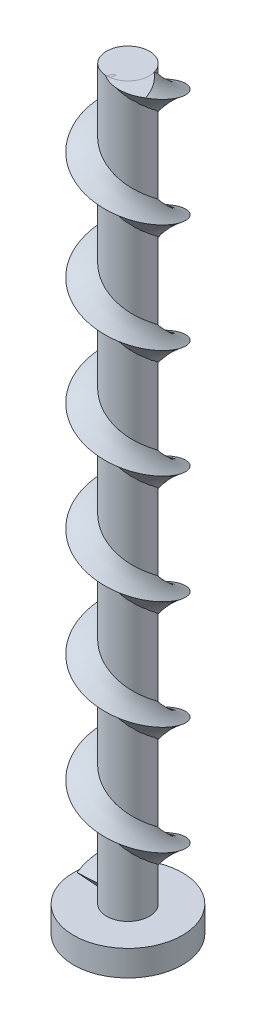
SolidWorks part; units mm, degrees
ref_plane "Front Plane" through (0, 0, 0) normal (0, 0, 1) x (1, 0, 0)
ref_plane "Top Plane" through (0, 0, 0) normal (0, 1, 0) x (1, 0, 0)
ref_plane "Right Plane" through (0, 0, 0) normal (1, 0, 0) x (0, 0, -1)
sketch "Sketch1" plane through (0, 0, 0) normal (0, 1, 0) x (1, 0, 0)
  line L1 (-2.5, 1.5) -> (2.5, 1.5)
  line L2 (-2.5, 1.5) -> (-2.5, -1.5)
  line L3 (-2.5, -1.5) -> (2.5, -1.5)
  line L4 (2.5, 1.5) -> (2.5, -1.5)
  circle A0 centre (0, 0) radius 12.7
  dimension "D1" = 5
  dimension "D2" = 3
  dimension "D3" = 1.5
  dimension "D4" = 2.5
extrude "Boss-Extrude1" add sketch "Sketch1" along normal blind 6
sketch "Sketch2" plane through (0, 6, 0) normal (0, 1, 0) x (1, 0, 0)
  circle A0 centre (0, 0) radius 5
extrude "Boss-Extrude2" add sketch "Sketch2" along normal blind 170
sketch "Sketch3" plane through (0, 6, 0) normal (0, 1, 0) x (1, 0, 0)
  circle A0 centre (0, 0) radius 5
curve "Helix/Spiral1" pitch 25.4 height 172.72 radius 5 left hand yes centre (0, 6, 0) axis (0, 1, 0) start towards (0, 0, 1)
ref_plane "Plane1" through (-5, 6, 0) normal (0, 0.6287, -0.7776) x (-1, 0, 0)
sketch "Sketch4" plane through (-5, 6, 0) normal (0, 0.6287, -0.7776) x (-1, 0, 0)
  line L0 (-1.0815, 4.5683) -> (-1.0815, -2.0595)
  line L2 (-1.0815, -2.0595) -> (5.1185, 2.8044)
  line L3 (5.1185, 2.8044) -> (-1.0815, 4.5683)
  dimension "D1" = 6.2
sweep "Sweep1" add profiles "Sketch4" path "Helix/Spiral1"
sketch "Sketch5" plane through (0, 176, 0) normal (0, 1, 0) x (1, 0, 0)
  circle A0 centre (0, 0) radius 43.5012
extrude "Cut-Extrude1" cut sketch "Sketch5" along normal through all
ref_plane "Plane2" through (0, 90, 0) normal (0, -1, 0) x (-1, 0, 0)
